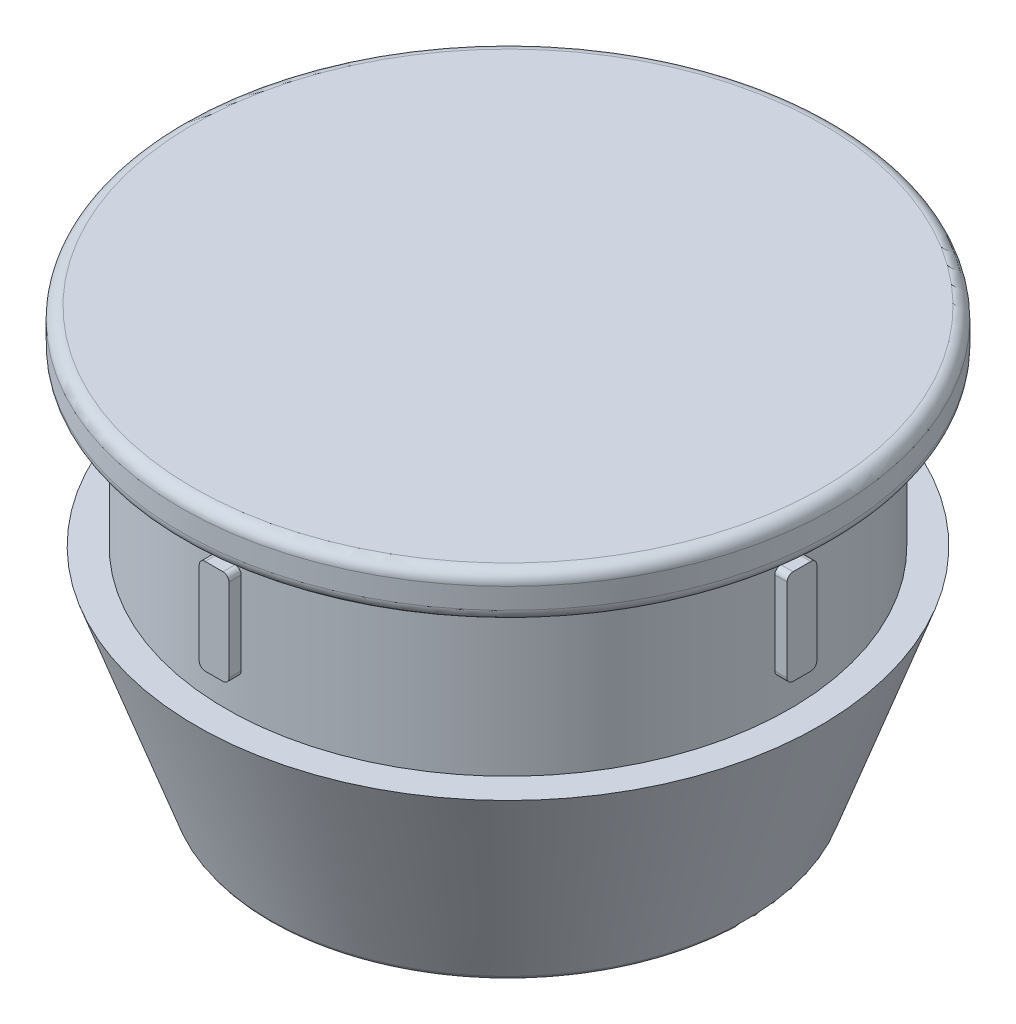
SolidWorks part; units mm, degrees
ref_plane "Front Plane" through (0, 0, 0) normal (0, 0, 1) x (1, 0, 0)
ref_plane "Top Plane" through (0, 0, 0) normal (0, 1, 0) x (1, 0, 0)
ref_plane "Right Plane" through (0, 0, 0) normal (1, 0, 0) x (0, 0, -1)
sketch "Sketch1" plane through (0, 0, 0) normal (0, 0, 1) x (1, 0, 0)
  line L0 (0, 0) -> (0, 129331.7353) construction
  line L1 (13.335, -6.985) -> (10.16, -15.875)
  line L2 (-12.7, -25.4) -> (12.7, -25.4) construction
  line L3 (-12.7, -25.4) -> (-12.7, 0) construction
  line L5 (12.7, -25.4) -> (12.7, 0) construction
  line L7 (10.16, -15.875) -> (9.525, -15.875)
  line L8 (9.525, -15.875) -> (9.525, 0)
  line L9 (9.525, 0) -> (0, 0)
  line L10 (0, 0) -> (0, 1.905)
  line L11 (0, 1.905) -> (13.97, 1.905)
  line L12 (12.065, 0) -> (12.065, -6.985)
  line L13 (12.065, -6.985) -> (13.335, -6.985)
  line L14 (12.065, 0) -> (13.97, 0)
  line L15 (13.97, 0) -> (13.97, 1.905)
  point P3 (0, 0)
  point P10 (0, -25.4)
  dimension "D1" = 25.4
  dimension "D2" = 25.4
  dimension "D3" = 26.67
  dimension "D4" = 8.89
  dimension "D5" = 1.905
  dimension "D6" = 2.54
  dimension "D7" = 20.32
  dimension "D8" = 24.13
  dimension "D9" = 17.78
  dimension "D10" = 27.94
revolve "Revolve1" add sketch "Sketch1" angle 360 about L0
ref_plane "Plane1" through (9.525, 0, 0) normal (-1, 0, 0) x (0, 0, 1)
sketch "Sketch2" plane through (9.525, 0, 0) normal (-1, 0, 0) x (0, 0, 1)
  line L0 (0, 0) -> (0, -6.985) construction
  line L1 (0.635, -1.4605) -> (-0.635, -1.4605)
  line L2 (0.635, -1.4605) -> (0.635, -5.5245)
  line L3 (0.635, -5.5245) -> (-0.635, -5.5245)
  line L4 (-0.635, -1.4605) -> (-0.635, -5.5245)
  line L5 (0.635, -1.4605) -> (-0.635, -5.5245) construction
  line L6 (0.635, -5.5245) -> (-0.635, -1.4605) construction
  line L7 (13.335, -6.985) -> (-13.335, -6.985) construction
  point P0 (0, -3.4925)
  point P9 (0, -3.4925)
  dimension "D1" = 4.064
  dimension "D2" = 1.27
extrude "Boss-Extrude1" add sketch "Sketch2" against normal blind 3.048
fillet "Fillet1" radius 0.508 4 edges at (0, 1.905, -13.97) (0, 0, -13.97) (0, 0, -9.525) (0, 0, -12.065)
fillet "Fillet2" radius 0.254 6 edges at (0, -15.875, -9.525) (0, -15.875, -10.16) (12.3106, -5.5245, 0.635) (12.3106, -1.4605, 0.635) (12.3106, -1.4605, -0.635) (12.3106, -5.5245, -0.635)
pattern_circular "CirPattern1" count 4 every 90 about axis through (0, 0, 0) along (0, -1, 0) of "Boss-Extrude1", "Fillet2"
